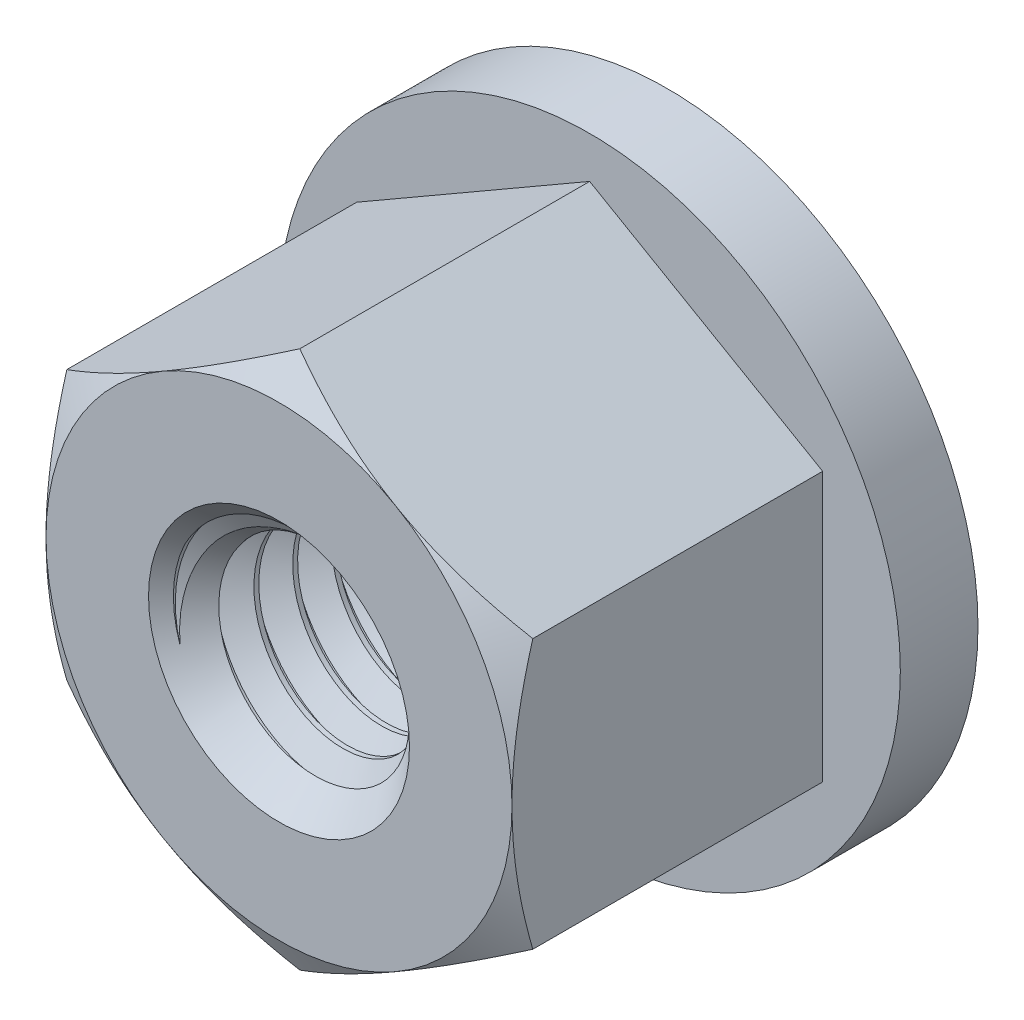
SolidWorks part; units mm, degrees
ref_plane "Front Plane" through (0, 0, 0) normal (0, 0, 1) x (1, 0, 0)
ref_plane "Top Plane" through (0, 0, 0) normal (0, 1, 0) x (1, 0, 0)
ref_plane "Right Plane" through (0, 0, 0) normal (1, 0, 0) x (0, 0, -1)
sketch "Sketch1" plane through (0, 0, 0) normal (0, 0, 1) x (1, 0, 0)
  line L1 (0, 5.4993) -> (-4.7625, 2.7496)
  line L2 (-4.7625, 2.7496) -> (-4.7625, -2.7496)
  line L3 (-4.7625, -2.7496) -> (0, -5.4993)
  line L4 (0, -5.4993) -> (4.7625, -2.7496)
  line L5 (4.7625, -2.7496) -> (4.7625, 2.7496)
  line L6 (4.7625, 2.7496) -> (0, 5.4993)
  circle A0 centre (0, 0) radius 4.7625 construction
  dimension "Hex" = 9.525
extrude "Extrude1" add sketch "Sketch1" against normal blind 7.9375
sketch "Sketch13" plane through (0, 0, -7.9375) normal (0, 0, -1) x (-1, 0, 0)
  circle A0 centre (0, 0) radius 6.35
  dimension "Flange od" = 12.7
extrude "Extrude3" add sketch "Sketch13" against normal blind 1.5875
sketch "Sketch2" plane through (0, 0, 0) normal (0, 0, 1) x (1, 0, 0)
  circle A0 centre (0, 0) radius 4.7625 construction
  circle A1 centre (0, 0) radius 4.7625
extrude "Cut-Extrude1" cut sketch "Sketch2" against normal through all draft 60 flip side to cut
sketch "Sketch4" plane through (0, 0, 0) normal (0, 0, 1) x (1, 0, 0)
  circle A0 centre (0, 0) radius 2.413
  dimension "Thread Dia" = 4.826
extrude "Cut-Extrude3" cut sketch "Sketch4" against normal through all
sketch "Sketch7" plane through (0, 0, 0) normal (0, 0, 1) x (1, 0, 0)
  circle A4 centre (0, 0) radius 2.667
  circle A5 centre (0, 0) radius 2.667
  dimension "D1" = 0.254
sketch "Sketch8" plane through (0, 0, -7.9375) normal (0, 0, -1) x (-1, 0, 0)
  circle A1 centre (0, 0) radius 2.667
  circle A2 centre (0, 0) radius 2.667 construction
sketch "Sketch5" plane through (0, 0, 0) normal (0, 0, 1) x (1, 0, 0)
  circle A0 centre (0, 0) radius 2.413 construction
  circle A1 centre (0, 0) radius 2.413
curve "Helix/Spiral1" pitch 0.7937 height 8.7312 turns 11 parameters "pitch"=0.7937
sketch "Sketch9" plane through (0, 0, 0) normal (1, 0, 0) x (0, 0, -1)
  line L0 (-0.3969, 2.413) -> (-0.2977, 2.413)
  line L1 (-0.2977, 2.413) -> (0, 1.8974)
  line L2 (-0.3969, 2.413) -> (-0.6945, 1.8974)
  line L3 (-0.6945, 1.8974) -> (0, 1.8974)
  line L4 (-0.3473, 2.413) -> (-0.3473, 1.8974) construction
  line L5 (-0.5457, 2.1552) -> (-0.1488, 2.1552) construction
  line L7 (0, 1.8974) -> (0, 2.413) construction
  line L8 (0, 2.413) -> (0, -2.413) construction
  dimension "D1" = 0.0992
  dimension "D2" = 0.3969
  dimension "D3" = 60
sketch "Sketch12" plane through (0, 0, 0) normal (0, 0, 1) x (1, 0, 0)
  circle A0 centre (0, 0) radius 1.8974
  circle A1 centre (0, 0) radius 2.413 construction
  circle A2 centre (0, 0) radius 2.413
extrude "Extrude2" add sketch "Sketch12" against normal up to surface (7.9375 mm away) up to face at (2.413, 0, -7.9375)
sweep "Cut-Sweep1" cut profiles "Sketch9" path "Helix/Spiral1"
extrude "Cut-Extrude6" cut sketch "Sketch7" against normal through all draft 45
extrude "Cut-Extrude7" cut sketch "Sketch8" against normal through all draft 45
equation "\"D2@Sketch9\" = \"pitch@Helix/Spiral1\"*.5"
equation "\"D3@Helix/Spiral1\" = \"pitch@Helix/Spiral1\"+\"Height@Extrude1\""
equation "\"D1@Sketch9\" = \"pitch@Helix/Spiral1\"*.125"
